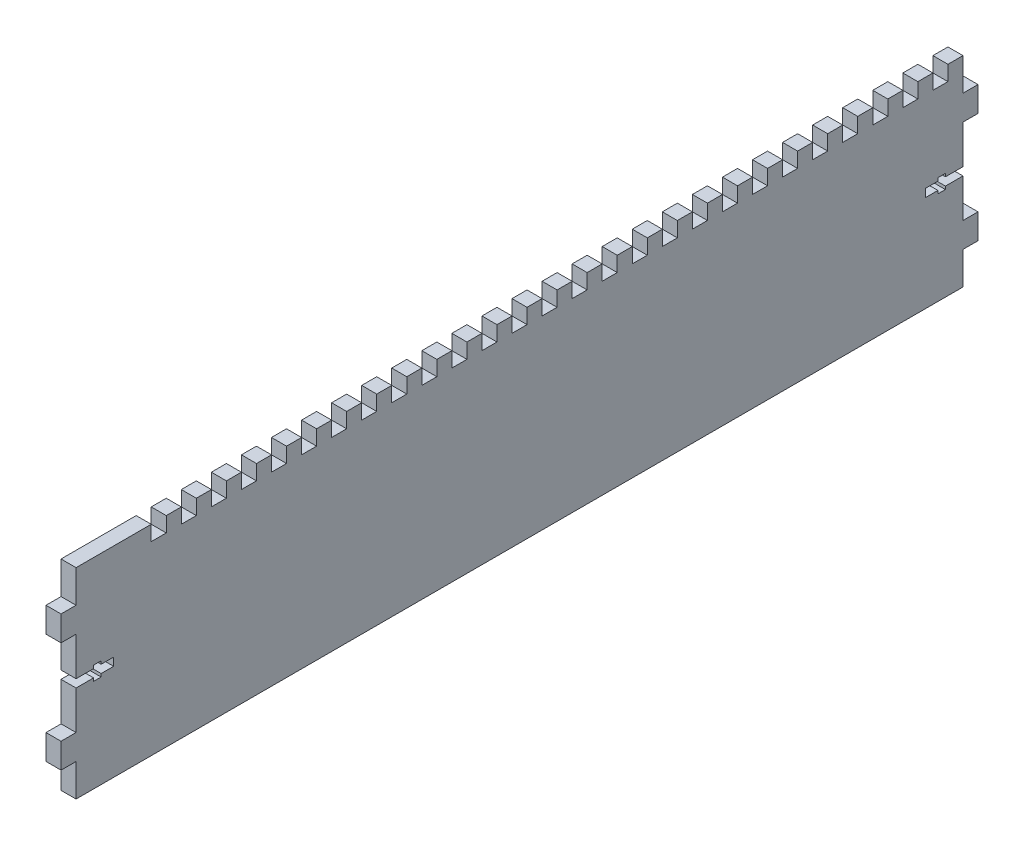
SolidWorks part; units mm, degrees
ref_plane "Front Plane" through (0, 0, 0) normal (0, 0, 1) x (1, 0, 0)
ref_plane "Top Plane" through (0, 0, 0) normal (0, 1, 0) x (1, 0, 0)
ref_plane "Right Plane" through (0, 0, 0) normal (1, 0, 0) x (0, 0, -1)
sketch "Sketch1" plane through (0, 0, 0) normal (1, 0, 0) x (0, 0, -1)
  line L1 (-177, -40) -> (177, -40)
  line L2 (-177, -40) -> (-177, 40)
  line L3 (-177, 40) -> (177, 40)
  line L4 (177, -40) -> (177, 40)
  line L5 (-177, -40) -> (177, 40) construction
  line L6 (-177, 40) -> (177, -40) construction
  point P0 (0, 0)
  dimension "D1" = 80
  dimension "D2" = 354
extrude "Boss-Extrude1" add sketch "Sketch1" along normal blind 6
sketch "Sketch3" plane through (0, 40, 0) normal (0, 1, 0) x (1, 0, 0)
  line L0 (-213.5, -147) -> (219.5, -147) construction
  line L1 (-213.5, 323) -> (-213.5, 177) construction
  line L2 (219.5, 323) -> (219.5, 177) construction
  line L3 (244.3, -177) -> (-238.3, -177) construction
  line L5 (0, -147) -> (6, -147)
  line L6 (0, -147) -> (0, -141)
  line L7 (0, -141) -> (6, -141)
  line L8 (6, -147) -> (6, -141)
  line L10 (6, -135) -> (6, -129)
  line L11 (0, -129) -> (6, -129)
  line L12 (0, -135) -> (0, -129)
  line L13 (0, -135) -> (6, -135)
  line L14 (6, -123) -> (6, -117)
  line L15 (0, -117) -> (6, -117)
  line L16 (0, -123) -> (0, -117)
  line L17 (0, -123) -> (6, -123)
  line L18 (6, -111) -> (6, -105)
  line L19 (0, -105) -> (6, -105)
  line L20 (0, -111) -> (0, -105)
  line L21 (0, -111) -> (6, -111)
  line L22 (6, -99) -> (6, -93)
  line L23 (0, -93) -> (6, -93)
  line L24 (0, -99) -> (0, -93)
  line L25 (0, -99) -> (6, -99)
  line L26 (6, -87) -> (6, -81)
  line L27 (0, -81) -> (6, -81)
  line L28 (0, -87) -> (0, -81)
  line L29 (0, -87) -> (6, -87)
  line L30 (6, -75) -> (6, -69)
  line L31 (0, -69) -> (6, -69)
  line L32 (0, -75) -> (0, -69)
  line L33 (0, -75) -> (6, -75)
  line L34 (6, -63) -> (6, -57)
  line L35 (0, -57) -> (6, -57)
  line L36 (0, -63) -> (0, -57)
  line L37 (0, -63) -> (6, -63)
  line L38 (6, -51) -> (6, -45)
  line L39 (0, -45) -> (6, -45)
  line L40 (0, -51) -> (0, -45)
  line L41 (0, -51) -> (6, -51)
  line L42 (6, -39) -> (6, -33)
  line L43 (0, -33) -> (6, -33)
  line L44 (0, -39) -> (0, -33)
  line L45 (0, -39) -> (6, -39)
  line L46 (6, -27) -> (6, -21)
  line L47 (0, -21) -> (6, -21)
  line L48 (0, -27) -> (0, -21)
  line L49 (0, -27) -> (6, -27)
  line L50 (6, -15) -> (6, -9)
  line L51 (0, -9) -> (6, -9)
  line L52 (0, -15) -> (0, -9)
  line L53 (0, -15) -> (6, -15)
  line L54 (6, -3) -> (6, 3)
  line L55 (0, 3) -> (6, 3)
  line L56 (0, -3) -> (0, 3)
  line L57 (0, -3) -> (6, -3)
  line L58 (6, 9) -> (6, 15)
  line L59 (0, 15) -> (6, 15)
  line L60 (0, 9) -> (0, 15)
  line L61 (0, 9) -> (6, 9)
  line L62 (6, 21) -> (6, 27)
  line L63 (0, 27) -> (6, 27)
  line L64 (0, 21) -> (0, 27)
  line L65 (0, 21) -> (6, 21)
  line L66 (6, 33) -> (6, 39)
  line L67 (0, 39) -> (6, 39)
  line L68 (0, 33) -> (0, 39)
  line L69 (0, 33) -> (6, 33)
  line L70 (6, 45) -> (6, 51)
  line L71 (0, 51) -> (6, 51)
  line L72 (0, 45) -> (0, 51)
  line L73 (0, 45) -> (6, 45)
  line L74 (6, 57) -> (6, 63)
  line L75 (0, 63) -> (6, 63)
  line L76 (0, 57) -> (0, 63)
  line L77 (0, 57) -> (6, 57)
  line L78 (6, 69) -> (6, 75)
  line L79 (0, 75) -> (6, 75)
  line L80 (0, 69) -> (0, 75)
  line L81 (0, 69) -> (6, 69)
  line L82 (6, 81) -> (6, 87)
  line L83 (0, 87) -> (6, 87)
  line L84 (0, 81) -> (0, 87)
  line L85 (0, 81) -> (6, 81)
  line L86 (6, 93) -> (6, 99)
  line L87 (0, 99) -> (6, 99)
  line L88 (0, 93) -> (0, 99)
  line L89 (0, 93) -> (6, 93)
  line L90 (6, 105) -> (6, 111)
  line L91 (0, 111) -> (6, 111)
  line L92 (0, 105) -> (0, 111)
  line L93 (0, 105) -> (6, 105)
  line L94 (6, 117) -> (6, 123)
  line L95 (0, 123) -> (6, 123)
  line L96 (0, 117) -> (0, 123)
  line L97 (0, 117) -> (6, 117)
  line L98 (6, 129) -> (6, 135)
  line L99 (0, 135) -> (6, 135)
  line L100 (0, 129) -> (0, 135)
  line L101 (0, 129) -> (6, 129)
  line L102 (6, 141) -> (6, 147)
  line L103 (0, 147) -> (6, 147)
  line L104 (0, 141) -> (0, 147)
  line L105 (0, 141) -> (6, 141)
  line L106 (6, 153) -> (6, 159)
  line L107 (0, 159) -> (6, 159)
  line L108 (0, 153) -> (0, 159)
  line L109 (0, 153) -> (6, 153)
  line L110 (6, 165) -> (6, 171)
  line L111 (0, 171) -> (6, 171)
  line L112 (0, 165) -> (0, 171)
  line L113 (0, 165) -> (6, 165)
  line L114 (0, 177) -> (0, -177) construction
  line L115 (6, 177) -> (6, -177) construction
  dimension "D1" = 30
  dimension "D2" = 6
  dimension "D3" = 27
extrude "Cut-Extrude2" cut sketch "Sketch3" against normal blind 6
sketch "Sketch4" plane through (0, 0, 177) normal (0, 0, 1) x (1, 0, 0)
  line L1 (6, 27) -> (0, 27) construction
  line L2 (6, 17) -> (6, 27) construction
  line L3 (0, 27) -> (0, 17) construction
  line L4 (0, 17) -> (6, 17) construction
  line L7 (6, -17) -> (0, -17) construction
  line L8 (6, -27) -> (6, -17) construction
  line L9 (0, -17) -> (0, -27) construction
  line L10 (0, -27) -> (6, -27) construction
  line L13 (6, 27) -> (0, 27)
  line L14 (6, 17) -> (6, 27)
  line L15 (0, 27) -> (0, 17)
  line L16 (0, 17) -> (6, 17)
  line L17 (6, -17) -> (0, -17)
  line L18 (6, -27) -> (6, -17)
  line L19 (0, -17) -> (0, -27)
  line L20 (0, -27) -> (6, -27)
extrude "Boss-Extrude2" add sketch "Sketch4" along normal blind 6
sketch "Sketch5" plane through (0, 0, 0) normal (-1, 0, 0) x (0, 0, 1)
  line L0 (177, 17) -> (177, -17) construction
  line L7 (0, 0) -> (0, -20.5925) construction
  line L8 (-177, 1.6) -> (-170, 1.6)
  line L9 (-167, 2.8) -> (-170, 2.8)
  line L10 (-167, 1.6) -> (-162, 1.6)
  line L11 (-162, -1.6) -> (-162, 1.6)
  line L12 (-167, -1.6) -> (-162, -1.6)
  line L13 (-167, -2.8) -> (-170, -2.8)
  line L14 (-177, -1.6) -> (-170, -1.6)
  line L15 (-170, -2.8) -> (-170, -1.6)
  line L16 (-170, 1.6) -> (-170, 2.8)
  line L17 (-167, 1.6) -> (-167, 2.8)
  line L18 (-167, -2.8) -> (-167, -1.6)
  line L19 (183, -1.6) -> (183, 1.6) construction
  line L20 (183, -1.6) -> (183, 1.6)
  line L21 (183, 0) -> (146.4296, 0) construction
  line L25 (177, -1.6) -> (177, 1.6)
  line L26 (167, -2.8) -> (167, -1.6)
  line L27 (167, 1.6) -> (167, 2.8)
  line L28 (170, 1.6) -> (170, 2.8)
  line L29 (170, -2.8) -> (170, -1.6)
  line L30 (177, -1.6) -> (170, -1.6)
  line L31 (167, -2.8) -> (170, -2.8)
  line L32 (167, -1.6) -> (162, -1.6)
  line L33 (162, -1.6) -> (162, 1.6)
  line L34 (167, 1.6) -> (162, 1.6)
  line L35 (167, 2.8) -> (170, 2.8)
  line L36 (177, 1.6) -> (170, 1.6)
  line L37 (-177, -1.6) -> (-177, 1.6)
  line L38 (-183, -1.6) -> (-183, 1.6)
  point P0 (177, 0)
  dimension "D1" = 15
  dimension "D2" = 5.6
  dimension "D3" = 3.2
  dimension "D4" = 7
  dimension "D5" = 3
extrude "Cut-Extrude3" cut sketch "Sketch5" against normal up to next contours L25 L36 L28 L35 L27 L34 L33 L32 L26 L31 L29 L30 | L37 L14 L15 L13 L18 L12 L11 L10 L17 L9 L16 L8 region at (0, 0, -169.3696) region at (0, 0, 169.3696)
sketch "Sketch7" plane through (0, 0, -177) normal (0, 0, -1) x (-1, 0, 0)
  line L1 (-6, 27) -> (0, 27)
  line L2 (-6, 27) -> (-6, 17)
  line L3 (-6, 17) -> (0, 17)
  line L4 (0, 27) -> (0, 17)
  line L6 (-6, -17) -> (0, -17)
  line L7 (-6, -17) -> (-6, -27)
  line L8 (-6, -27) -> (0, -27)
  line L9 (0, -17) -> (0, -27)
  line L11 (0, 1.6) -> (0, 40) construction
  line L12 (0, 17) -> (-6, 17) construction
  line L13 (-6, 1.6) -> (-6, 40) construction
  line L14 (-6, 27) -> (0, 27) construction
  line L15 (-6, -40) -> (-6, -1.6) construction
  line L16 (0, -40) -> (0, -1.6) construction
  line L17 (-6, -17) -> (0, -17) construction
  line L18 (0, -27) -> (-6, -27) construction
extrude "Boss-Extrude3" add sketch "Sketch7" along normal blind 6
